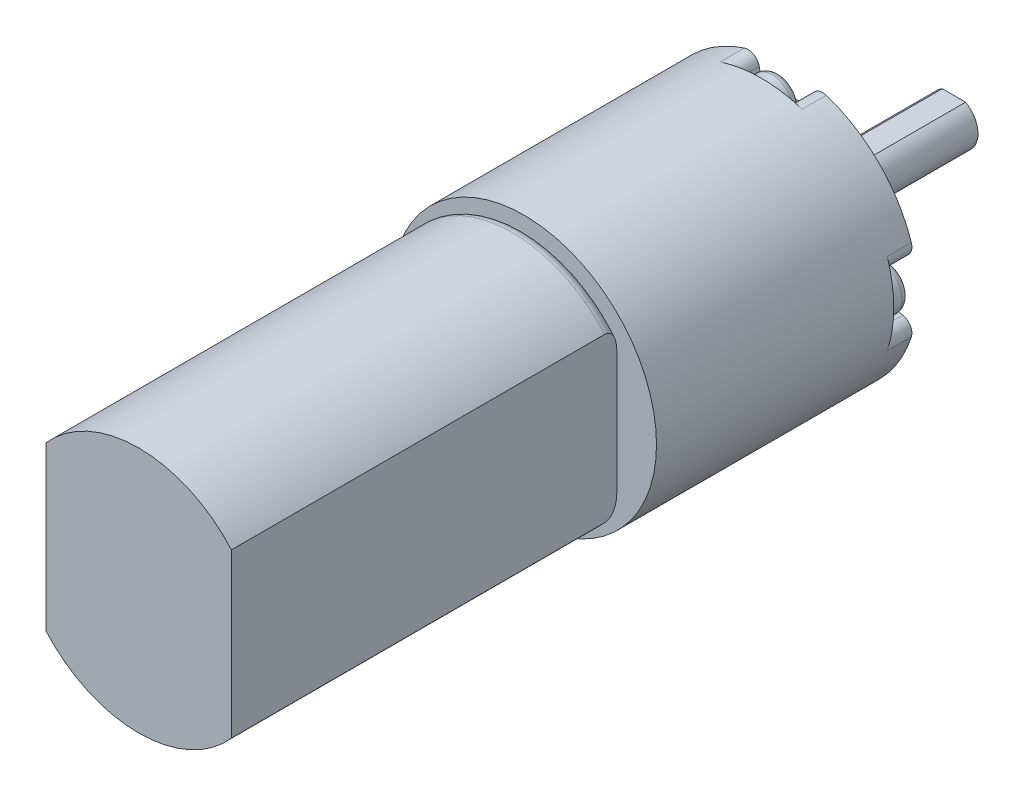
SolidWorks part; units mm, degrees
ref_plane "Plan de face" through (0, 0, 0) normal (0, 0, 1) x (1, 0, 0)
ref_plane "Plan de dessus" through (0, 0, 0) normal (0, 1, 0) x (1, 0, 0)
ref_plane "Plan de droite" through (0, 0, 0) normal (1, 0, 0) x (0, 0, -1)
sketch "Esquisse1" plane through (0, 0, 0) normal (1, 0, 0) x (0, 0, -1)
  line L0 (32, 9.25) -> (32, 11)
  line L1 (0, 0) -> (67.7, 0)
  line L2 (0, 0) -> (0, 10.253)
  line L3 (0, 10.253) -> (31, 10.253)
  line L4 (32, 9.25) -> (32, 9.253)
  line L6 (53.7, 7) -> (53.7, 11)
  line L7 (32, 11) -> (53.7, 11)
  line L8 (55.7, 2) -> (55.7, 7)
  line L11 (53.7, 7) -> (55.7, 7)
  line L14 (55.7, 2) -> (67.7, 2)
  line L15 (67.7, 0) -> (67.7, 2)
  arc A0 (31, 10.253) -> (32, 9.253) centre (31, 9.253) cw
  point P11 (32, 10.253)
  dimension "D1" = 1
revolve "Révolution2" add sketch "Esquisse1" angle 360 about L1 region at (0, 5.0708, -29.3056)
sketch "Esquisse4" plane through (0, 0, 0) normal (0, 0, 1) x (1, 0, 0)
  line L0 (7.7, 6.7701) -> (7.7, -6.7701)
  circle A0 centre (0, 0) radius 10.253 construction
  arc A1 (7.7, 6.7701) -> (7.7, -6.7701) centre (0, 0) cw
  dimension "D1" = 7.7
extrude "Enlèv. mat.-Extru.1" cut sketch "Esquisse4" against normal up to surface (32 mm away) up to face at (11, 0, -32)
sketch "Esquisse5" plane through (0, 0, -55.7) normal (0, 0, -1) x (-1, 0, 0)
  line L2 (-6, -3.6056) -> (-6, 3.6056)
  arc A3 (-6, 3.6056) -> (-6, -3.6056) centre (0, 0) ccw
  circle M1 centre (0, 0) radius 7
extrude "Enlèv. mat.-Extru.2" cut sketch "Esquisse5" against normal up to surface (2 mm away) contours L2 M1 region at (6.4026, 0, -55.7) up to face at (11, 0, -53.7)
mirror "Symétrie1" about plane through (0, 0, 0) normal (1, 0, 0) of "Enlèv. mat.-Extru.2", "Enlèv. mat.-Extru.1"
sketch "Esquisse6" plane through (0, 0, -67.7) normal (0, 0, -1) x (-1, 0, 0)
  line L0 (-0.9682, 1.75) -> (0.9682, 1.75)
  circle A0 centre (0, 0) radius 2 construction
  arc A1 (-0.9682, 1.75) -> (0.9682, 1.75) centre (0, 0) cw
  dimension "D1" = 1.75
extrude "Enlèv. mat.-Extru.3" cut sketch "Esquisse6" against normal up to surface (12 mm away) up to face at (2, 0, -55.7)
sketch "Esquisse7" plane through (0, 0, -53.7) normal (0, 0, -1) x (-1, 0, 0)
  line L0 (0, 0) -> (2.3862, 10.7381) construction
  line L1 (0, 0) -> (-2.3862, 10.7381) construction
  line L2 (-2, 9) -> (-2.1693, 9.7619)
  line L3 (2, 9) -> (2.1693, 9.7619)
  line L4 (0, 0) -> (0, 11) construction
  circle A0 centre (0, 0) radius 9 construction
  circle A1 centre (0, 9) radius 2 construction
  arc A2 (-2.1693, 9.7619) -> (-3.3958, 10.4627) centre (-3.1011, 9.5548) ccw
  circle A3 centre (0, 0) radius 11 construction
  circle A4 centre (0, 0) radius 10 construction
  arc A5 (-2, 9) -> (2, 9) centre (0, 9) ccw
  arc A6 (2.1693, 9.7619) -> (3.3958, 10.4627) centre (3.1011, 9.5548) cw
  arc A7 (-3.3958, 10.4627) -> (3.3958, 10.4627) centre (0, 0) cw
  circle M1 centre (0, 0) radius 11
extrude "Enlèv. mat.-Extru.4" cut sketch "Esquisse7" against normal blind 2 contours L3 A6 A2 L2 A5 M1 region at (0, 9.2427, -53.7)
sketch "Esquisse12" plane through (0, 0, -51.7) normal (0, 0, -1) x (-1, 0, 0)
  circle A0 centre (0, 9) radius 1.8
extrude "Boss.-Extru.2" add sketch "Esquisse12" along normal blind 1.5
fillet "Congé1" radius 0.6 1 edges at (-1.8, 9, -53.2)
sketch "Esquisse13" plane through (0, 0, -53.2) normal (0, 0, -1) x (-1, 0, 0)
  line L0 (-0.2, 9.2) -> (-0.2, 10)
  line L1 (-0.1321, 9) -> (0.1163, 9) construction
  line L2 (0, 9.1656) -> (0, 8.8469) construction
  line L3 (-0.2, 10) -> (0.2, 10) construction
  line L4 (0.2, 8) -> (0.2, 8.8)
  line L5 (-0.2, 8) -> (0.2, 8)
  line L6 (-0.2, 8.8) -> (-0.2, 8)
  line L7 (-1, 8.8) -> (-0.2, 8.8)
  line L8 (1, 9.2) -> (1, 8.8) construction
  line L9 (-0.2, 10) -> (0.2, 10)
  line L10 (0.2, 10) -> (0.2, 9.2)
  line L11 (0.2, 9.2) -> (1, 9.2)
  line L12 (1, 9.2) -> (1, 8.8)
  line L13 (1, 8.8) -> (0.2, 8.8)
  line L14 (-1, 9.2) -> (-1, 8.8)
  line L15 (-0.2, 9.2) -> (-1, 9.2)
  point P0 (0, 9)
extrude "Enlèv. mat.-Extru.6" cut sketch "Esquisse13" against normal blind 0.5
sketch "Esquisse17" plane through (0, 0, 0) normal (0, 1, 0) x (1, 0, 0)
  line L0 (0, 67.7) -> (0, 0) construction
  line L1 (0.9682, 67.7) -> (-0.9682, 67.7) construction
pattern_circular "Répétition circulaire1" count 4 every 90 about axis through (0, 0, 0) along (0, 0, 1) of "Enlèv. mat.-Extru.6", "Congé1", "Boss.-Extru.2", "Enlèv. mat.-Extru.4"
sketch "Esquisse18" plane through (0, 0, -53.7) normal (0, 0, -1) x (-1, 0, 0)
  line L1 (0, 0) -> (7.7782, 7.7782) construction
  circle A0 centre (0, 0) radius 9 construction
  arc A2 (10.4627, 3.3958) -> (3.3958, 10.4627) centre (0, 0) ccw construction
  circle A3 centre (6.364, 6.364) radius 1
extrude "Enlèv. mat.-Extru.7" cut sketch "Esquisse18" against normal blind 5
pattern_circular "Répétition circulaire2" count 4 every 90 about axis through (0, 0, 0) along (0, 0, 1) of "Enlèv. mat.-Extru.7"
